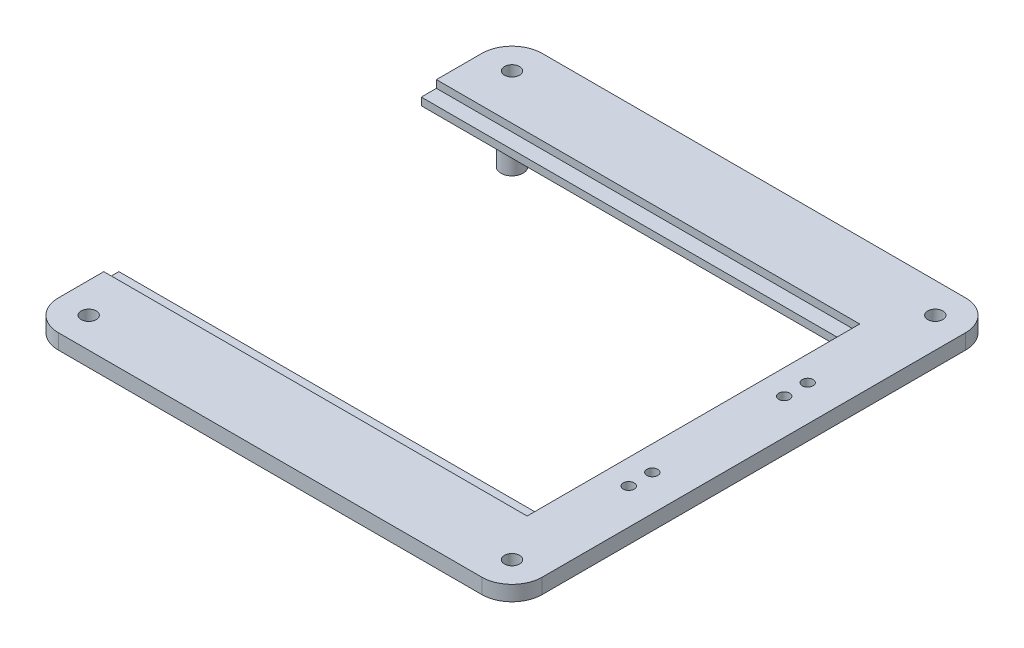
SolidWorks part; units mm, degrees
ref_plane "Front Plane" through (0, 0, 0) normal (0, 0, 1) x (1, 0, 0)
ref_plane "Top Plane" through (0, 0, 0) normal (0, 1, 0) x (1, 0, 0)
ref_plane "Right Plane" through (0, 0, 0) normal (1, 0, 0) x (0, 0, -1)
sketch "Sketch1" plane through (0, 0, 0) normal (0, 1, 0) x (1, 0, 0)
  line L0 (0, 0) -> (0, 25.4)
  line L1 (12.7, 38.1) -> (190.5, 38.1)
  line L2 (203.2, 25.4) -> (203.2, -152.4)
  line L3 (190.5, -165.1) -> (12.7, -165.1)
  line L4 (0, -152.4) -> (0, -127)
  line L5 (0, -127) -> (177.8, -127)
  line L6 (177.8, -127) -> (177.8, 0)
  line L7 (177.8, 0) -> (0, 0)
  arc A0 (12.7, -165.1) -> (0, -152.4) centre (12.7, -152.4) cw
  arc A1 (203.2, -152.4) -> (190.5, -165.1) centre (190.5, -152.4) cw
  arc A2 (190.5, 38.1) -> (203.2, 25.4) centre (190.5, 25.4) cw
  arc A3 (0, 25.4) -> (12.7, 38.1) centre (12.7, 25.4) cw
  point P13 (203.2, -165.1)
  point P16 (203.2, 38.1)
  point P19 (0, 38.1)
  dimension "D6" = 12.7
  dimension "D1" = 203.2
  dimension "D2" = 38.1
  dimension "D3" = 203.2
  dimension "D4" = 177.8
  dimension "D5" = 127
extrude "Boss-Extrude2" add sketch "Sketch1" along normal blind 6.35
sketch "Sketch2" plane through (0, 6.35, 0) normal (0, 1, 0) x (1, 0, 0)
  circle A0 centre (12.7, 25.4) radius 3.175
  circle A1 centre (190.5, 25.4) radius 3.175
  circle A2 centre (190.5, -152.4) radius 3.175
  circle A3 centre (12.7, -152.4) radius 3.175
  arc A4 (12.7, 38.1) -> (0, 25.4) centre (12.7, 25.4) ccw construction
  dimension "D1" = 6.35
extrude "Cut-Extrude1" cut sketch "Sketch2" against normal through all
sketch "Sketch5" plane through (0, 0, 0) normal (0, -1, 0) x (1, 0, 0)
  line L0 (0, 127) -> (0, 152.4) construction
  line L1 (12.7, 165.1) -> (190.5, 165.1) construction
  line L2 (203.2, 152.4) -> (203.2, -25.4) construction
  line L4 (203.2, 63.5) -> (0, 63.5) construction
  circle A0 centre (28.575, 136.525) radius 4.6625
  circle A1 centre (174.625, 136.525) radius 4.6625
  circle A4 centre (174.625, -9.525) radius 4.6625
  circle A5 centre (28.575, -9.525) radius 4.6625
  dimension "D1" = 28.575
  dimension "D2" = 28.575
  dimension "D3" = 9.325
  dimension "D4" = 28.575
  dimension "D5" = 28.575
extrude "Boss-Extrude3" add sketch "Sketch5" along normal blind 12.7
sketch "Sketch6" plane through (0, 6.35, 0) normal (0, 1, 0) x (1, 0, 0)
  line L0 (0, -127) -> (0, -152.4) construction
  line L1 (177.8, -127) -> (0, -127)
  line L2 (177.8, -127) -> (177.8, -133.35)
  line L3 (177.8, -133.35) -> (0, -133.35)
  line L4 (0, -127) -> (0, -133.35)
  line L5 (203.2, -63.5) -> (0, -63.5) construction
  line L6 (203.2, -152.4) -> (203.2, 25.4) construction
  line L7 (0, 0) -> (0, 6.35)
  line L8 (177.8, 6.35) -> (0, 6.35)
  line L9 (177.8, 0) -> (177.8, 6.35)
  line L10 (177.8, 0) -> (0, 0)
  dimension "D1" = 6.35
extrude "Cut-Extrude2" cut sketch "Sketch6" against normal blind 3.175
sketch "Sketch7" plane through (0, 6.35, 0) normal (0, 1, 0) x (1, 0, 0)
  line L0 (188.214, -28.194) -> (188.214, -33.528) construction
  line L1 (188.214, -38.1) -> (188.214, -88.9) construction
  line L2 (188.214, -93.472) -> (188.214, -98.806) construction
  line L3 (188.214, -23.622) -> (188.214, 38.1) construction
  line L4 (190.5, 38.1) -> (12.7, 38.1) construction
  line L5 (188.214, -103.378) -> (188.214, -165.1) construction
  line L6 (12.7, -165.1) -> (190.5, -165.1) construction
  line L7 (185.928, -25.908) -> (177.8, -25.908) construction
  line L8 (177.8, 6.35) -> (177.8, -133.35) construction
  circle A0 centre (188.214, -101.092) radius 2.286
  circle A1 centre (188.214, -91.186) radius 2.286
  circle A2 centre (188.214, -35.814) radius 2.286
  circle A3 centre (188.214, -25.908) radius 2.286
  dimension "D1" = 4.572
  dimension "D2" = 5.334
  dimension "D3" = 5.334
  dimension "D4" = 50.8
  dimension "D5" = 8.128
extrude "Cut-Extrude3" cut sketch "Sketch7" against normal blind 12.7
